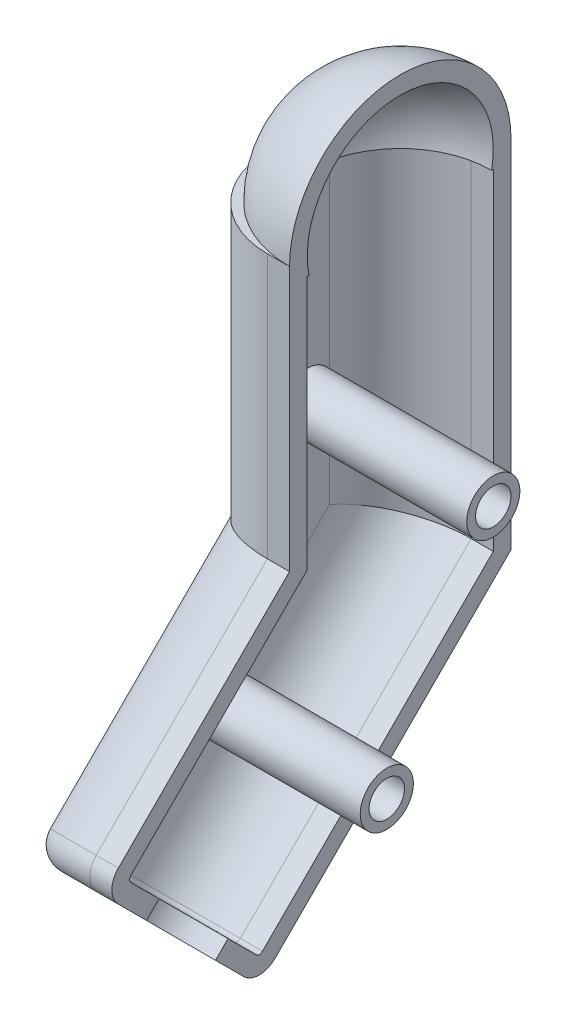
SolidWorks part; units mm, degrees
ref_plane "Front Plane" through (0, 0, 0) normal (0, 0, 1) x (1, 0, 0)
ref_plane "Top Plane" through (0, 0, 0) normal (0, 1, 0) x (1, 0, 0)
ref_plane "Right Plane" through (0, 0, 0) normal (1, 0, 0) x (0, 0, -1)
sketch "Sketch1" plane through (0, 0, 0) normal (1, 0, 0) x (0, 0, -1)
  line L0 (-12.5, 0) -> (12.5, 0)
  line L1 (-33.5876, -50.9099) -> (-15.9099, -68.5876)
  line L2 (-12.5, 0) -> (-12.5, -29.8223)
  line L3 (-12.5, -29.8223) -> (-33.5876, -50.9099)
  line L4 (12.5, 0) -> (12.5, -40.1777)
  line L5 (12.5, -40.1777) -> (-15.9099, -68.5876)
extrude "Boss-Extrude1" add sketch "Sketch1" along normal mid plane 25
sketch "Sketch2" plane through (0, 0, 0) normal (0, 0, 1) x (1, 0, 0)
  line L0 (0, 0) -> (0, 12.5)
  line L1 (0, 0) -> (-12.5, 0)
  arc A0 (0, 12.5) -> (-12.5, 0) centre (0, 0) ccw
revolve "Revolve1" add sketch "Sketch2" angle 360 about L0
fillet "Fillet1" radius 10 8 edges at (-12.5, -54.3826, 1.705) (-12.5, -20.0888, -12.5) (12.5, -54.3826, 1.705) (12.5, -20.0888, -12.5) (-12.5, -40.3661, 23.0438) (12.5, -40.3661, 23.0438) (12.5, -14.9112, 12.5) (-12.5, -14.9112, 12.5)
fillet "Fillet2" radius 2.5 8 edges at (-9.5711, -52.981, 31.5165) (-12.5, -59.7487, 24.7487) (-9.5711, -66.5165, 17.981) (0, -68.5876, 15.9099) (9.5711, -66.5165, 17.981) (12.5, -59.7487, 24.7487) (9.5711, -52.981, 31.5165) (0, -50.9099, 33.5876)
sketch "Sketch3" plane through (-12.5, 0, 0) normal (1, 0, 0) x (0, 0, -1)
  circle A0 centre (0, 0) radius 3.55
sketch "Sketch4" plane through (0, 0, 0) normal (0, 0, 1) x (1, 0, 0)
  line L0 (0, 17.0315) -> (0, -73.6851)
  line L4 (0, -73.6851) -> (29.5529, -73.6851)
  line L5 (29.5529, -73.6851) -> (29.5529, 17.0315)
  line L6 (29.5529, 17.0315) -> (0, 17.0315)
extrude "Cut-Extrude2" cut sketch "Sketch4" against normal mid plane 68.5
shell "Shell2" thickness 2 removed face at (0, -36.7115, 12.024)
extrude "Cut-Extrude3" cut sketch "Sketch3" along normal blind 12.5
sketch "Sketch6" plane through (-10.5, 0, 0) normal (-1, 0, 0) x (0, 0, 1)
  circle A0 centre (0, -24.45) radius 3
  circle A1 centre (12.0208, -47.0208) radius 3
extrude "Boss-Extrude3" add sketch "Sketch6" against normal blind 21
sketch "Sketch7" plane through (10.5, 0, 0) normal (1, 0, 0) x (0, 0, -1)
  circle A0 centre (0, -24.45) radius 2
  circle A1 centre (-12.0208, -47.0208) radius 2
extrude "Cut-Extrude4" cut sketch "Sketch7" against normal blind 21
sketch "Sketch8" plane through (0, -42.2487, 42.2487) normal (0, -0.7071, 0.7071) x (1, 0, 0)
  line L0 (0, -34.7487) -> (0, -14.7487) construction
  circle A0 centre (0, -24.7487) radius 5.5
extrude "Cut-Extrude5" cut sketch "Sketch8" against normal blind 5
